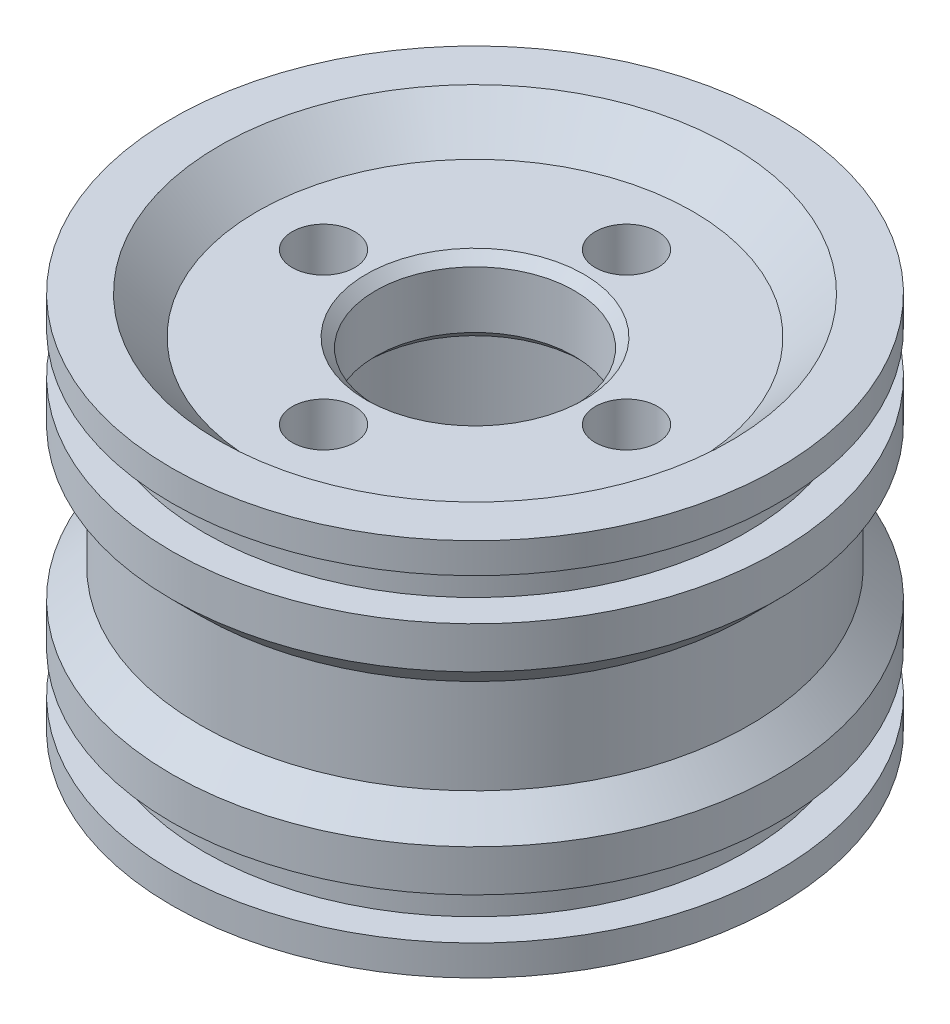
SolidWorks part; units mm, degrees
ref_plane "前视基准面" through (0, 0, 0) normal (0, 0, 1) x (1, 0, 0)
ref_plane "上视基准面" through (0, 0, 0) normal (0, 1, 0) x (1, 0, 0)
ref_plane "右视基准面" through (0, 0, 0) normal (1, 0, 0) x (0, 0, -1)
other "Configuration Table"
sketch "草图1" plane through (0, 0, 0) normal (0, 1, 0) x (1, 0, 0)
  circle A0 centre (0, 0) radius 16
  dimension "D1" = 32
extrude "凸台-拉伸1" add sketch "草图1" along normal mid plane 20
sketch "草图2" plane through (0, 0, 0) normal (0, 0, 1) x (1, 0, 0)
  line L0 (16, -10) -> (16, 10) construction
  line L1 (16, 8.4) -> (0, 8.4) construction
  line L2 (16, 8.4) -> (16, 6.2) construction
  line L3 (16, 6.2) -> (0, 6.2) construction
  line L4 (0, 8.4) -> (0, 6.2) construction
  line L5 (16, 10) -> (-16, 10) construction
  line L7 (16, 8.4) -> (14.3, 8.4)
  line L8 (16, 8.4) -> (16, 6.2)
  line L9 (16, 6.2) -> (14.3, 6.2)
  line L10 (14.3, 8.4) -> (14.3, 6.2)
  dimension "D1" = 2.2
  dimension "D2" = 1.6
  dimension "D3" = 1.7
revolve "切除-旋转1" cut sketch "草图2" angle 360 about L4
mirror "镜向1" about plane through (0, 0, 0) normal (0, 1, 0) of "切除-旋转1"
sketch "草图4" plane through (0, -10, 0) normal (0, -1, 0) x (1, 0, 0)
  circle A0 centre (0, 0) radius 11.5
  dimension "D1" = 23
extrude "切除-拉伸1" cut sketch "草图4" against normal blind 14
sketch "草图5" plane through (0, 10, 0) normal (0, 1, 0) x (1, 0, 0)
  circle A0 centre (0, 0) radius 5.25
  dimension "D1" = 10.5
extrude "切除-拉伸2" cut sketch "草图5" against normal blind 15 contours A0 region at (0, 10, 0)
chamfer "倒角1" distance 2 angle 45 1 edges at (0, -10, -11.5)
sketch "草图6" plane through (0, 10, 0) normal (0, 1, 0) x (1, 0, 0)
  circle A0 centre (0, 0) radius 5
  circle A1 centre (0, 0) radius 11.5
  dimension "D1" = 23
  dimension "D2" = 10
extrude "切除-拉伸3" cut sketch "草图6" against normal blind 2
chamfer "倒角2" distance 2 angle 45 1 edges at (0, 10, 11.5)
ref_axis "基准轴1" through (0, 4, 0) along (0, 1, 0)
sketch "草图7" plane through (0, 0, 0) normal (1, 0, 0) x (0, 0, -1)
  line L0 (16, -6.2) -> (16, 6.2) construction
  line L1 (14.5, -4) -> (16, -4)
  line L2 (14.5, -4) -> (14.5, 4)
  line L3 (14.5, 4) -> (16, 4)
  line L4 (16, -4) -> (16, 4)
  line L5 (14.5, -4) -> (16, 4) construction
  line L6 (14.5, 4) -> (16, -4) construction
  point P0 (15.25, 0)
  dimension "D1" = 1.5
  dimension "D2" = 8
sketch "草图8" plane through (0, 4, 0) normal (0, -1, 0) x (1, 0, 0)
  circle A0 centre (-8, 0) radius 1.65
  dimension "D1" = 3.3
  dimension "D2" = 8
extrude "切除-拉伸4" cut sketch "草图8" against normal blind 10
pattern_circular "阵列(圆周)1" count 4 over 360 about axis through (0, 4, 0) along (0, 1, 0) of "切除-拉伸4"
revolve "切除-旋转2" cut sketch "草图7" angle 360 about axis through (0, 4, 0) along (0, 1, 0)
chamfer "倒角5" distance 1.5 angle 45 2 edges at (0, 4, -14.5) (0, -4, -14.5)
chamfer "倒角4" distance 0.5 angle 45 3 edges at (0, 4, -11.5) (0, 8, 5.25) (0, 4, -5.25)
sketch "草图9" plane through (0, 0, 0) normal (0, 0, 1) x (1, 0, 0)
  line L0 (16, 10) -> (-16, 10) construction
  circle A0 centre (0, 3) radius 1.5
  dimension "D2" = 3
  dimension "D1" = 7
